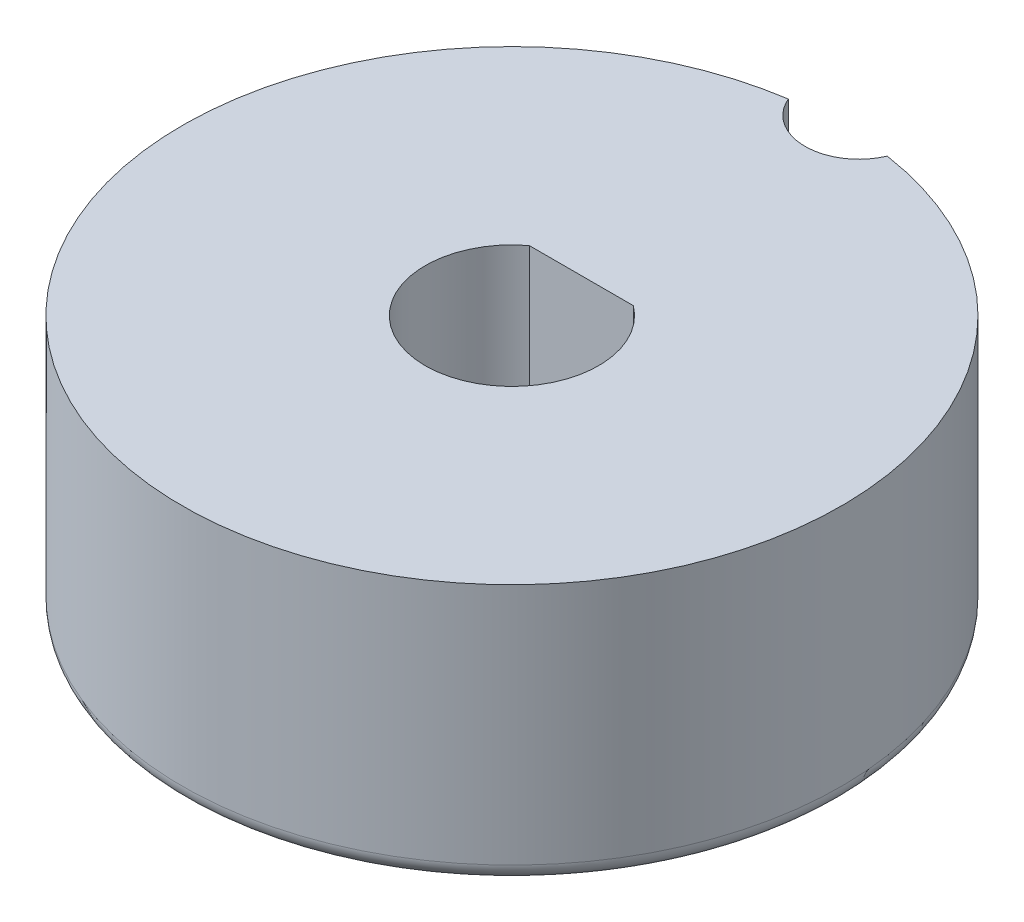
SolidWorks part; units mm, degrees
ref_plane "Front Plane" through (0, 0, 0) normal (0, 0, 1) x (1, 0, 0)
ref_plane "Top Plane" through (0, 0, 0) normal (0, 1, 0) x (1, 0, 0)
ref_plane "Right Plane" through (0, 0, 0) normal (1, 0, 0) x (0, 0, -1)
sketch "Sketch1" plane through (0, 0, 0) normal (0, 1, 0) x (1, 0, 0)
  line L0 (0, 10) -> (0, 9.5) construction
  circle A0 centre (0, 0) radius 9.5
  circle A1 centre (0, 0) radius 2.5
  circle A2 centre (0, 10) radius 1.55
  dimension "D1" = 19
  dimension "D2" = 5
  dimension "D3" = 3.1
  dimension "D4" = 0.5
extrude "Boss-Extrude1" add sketch "Sketch1" along normal blind 7.5 contours A2 A0 A1 | A0 A2 region at (-6.0182, 0, 7.0009) region at (0, 0, -9.0447)
extrude "Boss-Extrude2" add sketch "Sketch1<3>" along normal blind 2 contours A1
sketch "Sketch1<3>" plane through (0, 0, 0) normal (0, 1, 0) x (1, 0, 0) same geometry as "Sketch1"
ref_axis "Axis1" through (0, 0, 0) along (0, 1, 0)
extrude "Cut-Extrude1" cut sketch "Sketch1<4>" along normal through all contours A2
sketch "Sketch1<4>" plane through (0, 0, 0) normal (0, 1, 0) x (1, 0, 0) same geometry as "Sketch1"
sketch "Sketch2" plane through (0, 7.5, 0) normal (0, 1, 0) x (1, 0, 0)
  line L0 (1.5, 2) -> (-1.5, 2)
  line L1 (0, 0) -> (0, 10) construction
  circle A0 centre (0, 0) radius 2.5 construction
  circle A2 centre (0, 10) radius 2
  arc A3 (1.5, 2) -> (-1.5, 2) centre (0, 0) ccw
  point P7 (0, 10)
  point P15 (0, 0)
  circle M23 centre (0, 0) radius 2.5
  dimension "D1" = 4
  dimension "D2" = 2
extrude "Boss-Extrude3" add sketch "Sketch2" against normal up to surface (7.5 mm away) contours L1 L0 A3 | L0 L1 M23 region at (0.5708, 7.5, -2.2018) region at (-0.5708, 7.5, -2.2018) up to face at (0, 0, 0.525)
fillet "Fillet2" radius 3 rebuild error yes
fillet "Fillet1" radius 0.5 2 edges at (0, 0, 9.5) (0, 0, -8.45)
